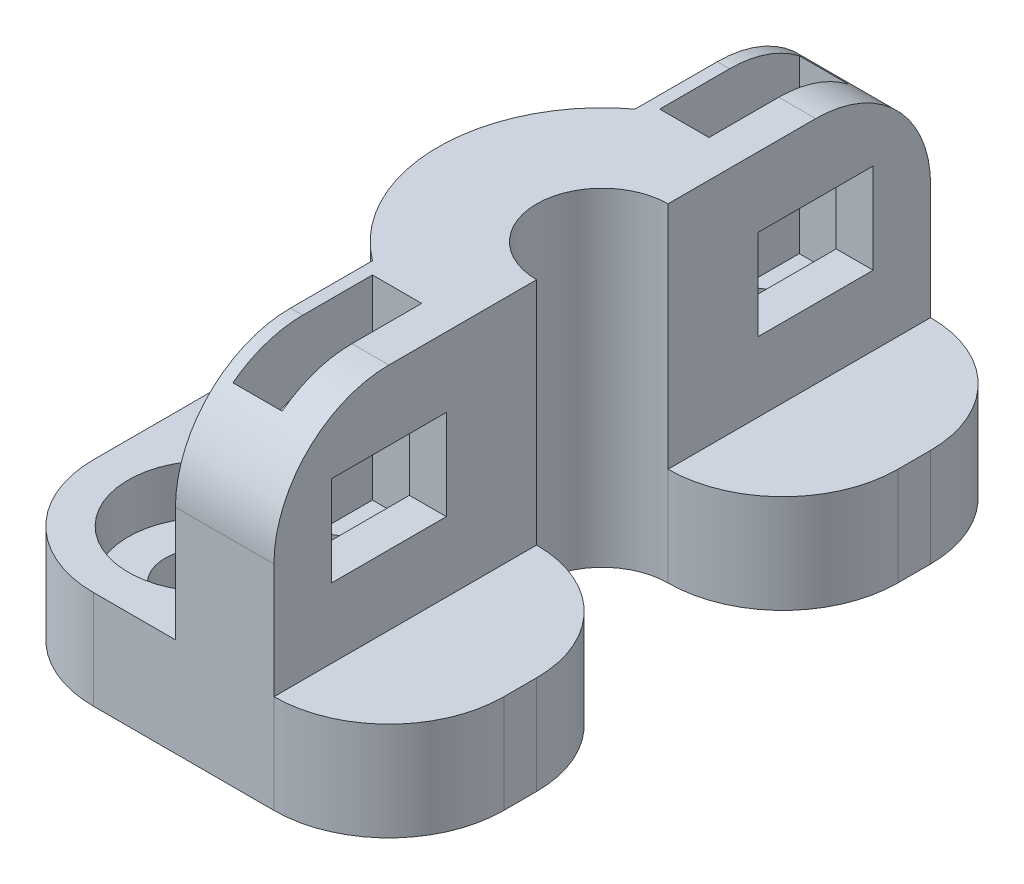
SolidWorks part; units mm, degrees
material "ABS"
ref_plane "Front Plane" through (0, 0, 0) normal (0, 0, 1) x (1, 0, 0)
ref_plane "Top Plane" through (0, 0, 0) normal (0, 1, 0) x (1, 0, 0)
ref_plane "Right Plane" through (0, 0, 0) normal (1, 0, 0) x (0, 0, -1)
sketch "Sketch1" plane through (0, 0, 0) normal (0, 1, 0) x (1, 0, 0)
  line L1 (-9, 20) -> (9, 20)
  line L2 (-9, 20) -> (-9, -20)
  line L3 (-9, -20) -> (9, -20)
  line L4 (9, 20) -> (9, -20)
  line L5 (-9, 20) -> (9, -20) construction
  line L6 (-9, -20) -> (9, 20) construction
  point P0 (0, 0)
  dimension "D1" = 18
  dimension "D2" = 40
extrude "Boss-Extrude1" add sketch "Sketch1" along normal blind 6
ref_axis "Axis1" through (9, 6, 0) along (0, 1, 0)
sketch "Sketch2" plane through (0, 6, 0) normal (0, 1, 0) x (1, 0, 0)
  line L0 (3, -20) -> (3, -8)
  line L1 (-9, -20) -> (9, -20) construction
  line L2 (3, 20) -> (3, 8)
  line L3 (9, 20) -> (-9, 20) construction
  line L4 (9, -20) -> (9, 20) construction
  line L9 (9, -20) -> (9, 20)
  line L10 (9, 20) -> (-9, 20)
  line L11 (-9, 20) -> (-9, -20)
  line L12 (-9, -20) -> (9, -20)
  line L13 (9, -20) -> (9, 20)
  line L14 (9, 20) -> (3, 20)
  line L16 (3, -20) -> (9, -20)
  arc A0 (3, 8) -> (3, -8) centre (9, 0) ccw
  dimension "D2" = 10
  dimension "D1" = 6
  dimension "D3" = 0
extrude "Boss-Extrude2" add sketch "Sketch2" along normal blind 14
sketch "Sketch3" plane through (0, 20, 0) normal (0, 1, 0) x (1, 0, 0)
  line L0 (9, -20) -> (9, 20) construction
  circle A0 centre (9, 0) radius 4
  dimension "D1" = 8
extrude "Cut-Extrude1" cut sketch "Sketch3" against normal through all
fillet "Fillet1" radius 7 2 edges at (6, 20, 20) (6, 20, -20)
sketch "Sketch12" plane through (0, 20, 0) normal (0, 1, 0) x (1, 0, 0)
  line L0 (16, 13) -> (9, 13) construction
  line L1 (3.75, 17.25) -> (6.75, 17.25)
  line L2 (3.75, 17.25) -> (3.75, 8.75)
  line L3 (3.75, 8.75) -> (6.75, 8.75)
  line L4 (6.75, 17.25) -> (6.75, 8.75)
  line L5 (3.75, 17.25) -> (6.75, 8.75) construction
  line L6 (3.75, 8.75) -> (6.75, 17.25) construction
  line L7 (9, 4) -> (9, 13) construction
  line L8 (0, 0) -> (24.0862, 0) construction
  line L9 (3.75, -8.75) -> (6.75, -17.25) construction
  line L10 (3.75, -17.25) -> (6.75, -8.75) construction
  line L11 (6.75, -17.25) -> (6.75, -8.75)
  line L12 (3.75, -8.75) -> (6.75, -8.75)
  line L13 (3.75, -17.25) -> (3.75, -8.75)
  line L14 (3.75, -17.25) -> (6.75, -17.25)
  point P0 (5.25, 13)
  point P16 (5.25, -13)
  dimension "D1" = 3
  dimension "D2" = 8.5
  dimension "D3" = 2.25
extrude "Cut-Extrude7" cut sketch "Sketch12" against normal blind 11.875
sketch "Sketch13" plane through (0, 8.125, 0) normal (0, 1, 0) x (1, 0, 0)
  line L0 (0, 0) -> (25.8503, 0) construction
  line L1 (6.75, 8.75) -> (6.75, 17.25) construction
  line L2 (6.75, 17.25) -> (3.75, 17.25) construction
  circle A0 centre (5.25, 13) radius 1.5
  circle A1 centre (5.25, -13) radius 1.5
  point P7 (6.75, 13)
  point P10 (5.25, 17.25)
  dimension "D1" = 3
extrude "Cut-Extrude8" cut sketch "Sketch13" against normal through all
sketch "Sketch14" plane through (3, 0, 0) normal (-1, 0, 0) x (0, 0, 1)
  line L0 (0, 0) -> (0, 34.28) construction
  line L1 (-20, 13) -> (-20, 6) construction
  line L2 (-13, 20) -> (-8, 20) construction
  circle A0 centre (-13, 13) radius 3
  circle A1 centre (13, 13) radius 3
  dimension "D1" = 6
  dimension "D2" = 7
  dimension "D3" = 7
extrude "Cut-Extrude9" cut sketch "Sketch14" against normal up to next
sketch "Sketch15" plane through (9, 0, 0) normal (1, 0, 0) x (0, 0, -1)
  line L0 (4, 20) -> (13, 20) construction
  line L1 (9.5, 15.75) -> (16.5, 15.75)
  line L2 (9.5, 15.75) -> (9.5, 10.25)
  line L3 (9.5, 10.25) -> (16.5, 10.25)
  line L4 (16.5, 15.75) -> (16.5, 10.25)
  line L5 (9.5, 15.75) -> (16.5, 10.25) construction
  line L6 (9.5, 10.25) -> (16.5, 15.75) construction
  line L7 (20, 13) -> (20, 0) construction
  line L8 (0, 0) -> (0, 22.7406) construction
  line L9 (-9.5, 10.25) -> (-16.5, 15.75) construction
  line L10 (-9.5, 15.75) -> (-16.5, 10.25) construction
  line L11 (-16.5, 15.75) -> (-16.5, 10.25)
  line L12 (-9.5, 10.25) -> (-16.5, 10.25)
  line L13 (-9.5, 15.75) -> (-9.5, 10.25)
  line L14 (-9.5, 15.75) -> (-16.5, 15.75)
  point P0 (13, 13)
  point P16 (-13, 13)
  dimension "D1" = 7
  dimension "D2" = 7
  dimension "D3" = 7
  dimension "D4" = 5.5
extrude "Cut-Extrude10" cut sketch "Sketch15" against normal up to next
sketch "Sketch7" plane through (9, 0, 0) normal (1, 0, 0) x (0, 0, -1)
  line L0 (-4, 0) -> (-4, 20) construction
  line L1 (-20, 0) -> (-4, 0)
  line L2 (-20, 0) -> (-20, 6)
  line L3 (-20, 6) -> (-4, 6)
  line L4 (-4, 0) -> (-4, 6)
  line L5 (0, 0) -> (0, 22.2367) construction
  line L6 (4, 0) -> (4, 6)
  line L7 (20, 6) -> (4, 6)
  line L8 (20, 0) -> (20, 6)
  line L9 (20, 0) -> (4, 0)
extrude "Boss-Extrude3" add sketch "Sketch7" along normal blind 7
fillet "Fillet2" radius 7 6 edges at (-9, 3, -20) (16, 3, -20) (16, 3, 20) (-9, 3, 20) (16, 3, -4) (16, 3, 4)
sketch "Sketch8" plane through (0, 6, 0) normal (0, 1, 0) x (1, 0, 0)
  line L0 (0, 0) -> (-13.0298, 0) construction
  circle A0 centre (-2, 13) radius 2.625
  circle A1 centre (-2, -13) radius 2.625
  dimension "D1" = 5.25
extrude "Cut-Extrude4" cut sketch "Sketch8" against normal through all
sketch "Sketch9" plane through (0, 0, 0) normal (0, 0, 1) x (1, 0, 0)
  line L0 (-9, 6) -> (2, 17)
  line L1 (2, 17) -> (2, 6)
  line L2 (-2, 6) -> (3, 6) construction
  line L3 (2, 6) -> (-9, 6)
  dimension "D1" = 45
  dimension "D2" = 11
extrude "Boss-Extrude4" add sketch "Sketch9" along normal blind 2.5 and the other way blind 2.5
sketch "Sketch10" plane through (0, 6, 0) normal (0, 1, 0) x (1, 0, 0)
  line L0 (0, 0) -> (-21.7297, 0) construction
  circle A0 centre (-2, 13) radius 4.875
  circle A1 centre (-2, -13) radius 4.875
  dimension "D1" = 9.75
extrude "Cut-Extrude5" cut sketch "Sketch10" against normal blind 3
